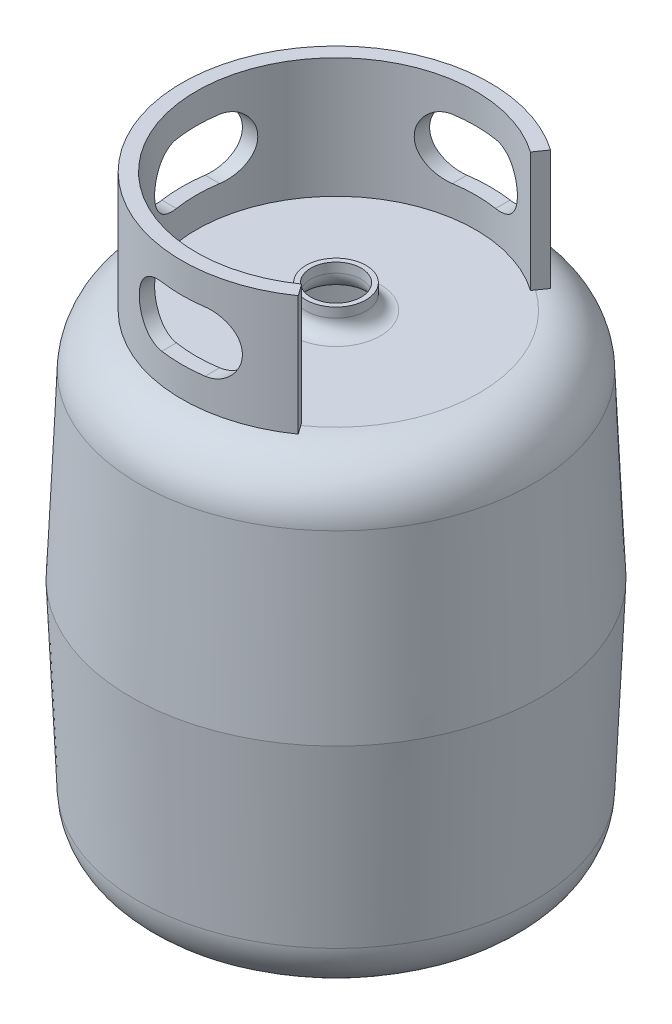
SolidWorks part; units mm, degrees
material "1060 Alloy"
ref_plane "Front Plane" through (0, 0, 0) normal (0, 0, 1) x (1, 0, 0)
ref_plane "Top Plane" through (0, 0, 0) normal (0, 1, 0) x (1, 0, 0)
ref_plane "Right Plane" through (0, 0, 0) normal (1, 0, 0) x (0, 0, -1)
sketch "Sketch6" plane through (0, 0, 0) normal (0, 0, 1) x (1, 0, 0)
  line L0 (0, -456.4408) -> (0, 456.4408) construction
  line L1 (-558.8873, 0) -> (558.8873, 0) construction
  line L2 (0, 213.75) -> (-25, 213.75)
  line L3 (-25, 213.75) -> (-25, 205.75)
  line L4 (-37, 193.75) -> (-119.4219, 193.75)
  line L5 (-164.379, 150.7129) -> (-170.9593, 0)
  line L6 (-170.9593, 0) -> (-164.379, -150.7129)
  line L7 (-119.4219, -193.75) -> (0, -193.75)
  line L8 (0, 213.75) -> (0, -193.75)
  arc A0 (-37, 193.75) -> (-25, 205.75) centre (-37, 205.75) ccw
  arc A1 (-164.379, -150.7129) -> (-119.4219, -193.75) centre (-119.4219, -148.75) ccw
  arc A2 (-119.4219, 193.75) -> (-164.379, 150.7129) centre (-119.4219, 148.75) ccw
  point P4 (0, 0)
  point P8 (0, 0)
  point P10 (-310.657, 0)
  point P18 (-25, 193.75)
  point P21 (-162.5, -193.75)
  point P24 (-162.5, 193.75)
  dimension "D9" = 12
  dimension "D10" = 45
  dimension "D1" = 387.5
  dimension "D2" = 25
  dimension "D3" = 20
  dimension "D4" = 162.5
  dimension "D5" = 162.5
  dimension "D6" = 193.75
  dimension "D7" = 193.75
  dimension "D8" = 92.5
revolve "Revolve2" add sketch "Sketch6" angle 360 about L8
shell "Shell8" thickness 4 removed face at (-25, 213.75, 0)
sketch "Sketch7" plane through (0, 193.75, 0) normal (0, 1, 0) x (1, 0, 0)
  line L0 (0, -178.349) -> (0, 178.349) construction
  line L1 (-198.7754, 0) -> (198.7754, 0) construction
  line L2 (0, 0) -> (73.6598, 105.197)
  line L3 (0, 0) -> (73.6598, -105.197)
  arc A0 (73.6598, 105.197) -> (73.6598, -105.197) centre (0, 0) ccw
  arc A1 (66.7768, 95.3672) -> (66.7768, -95.3672) centre (0, 0) ccw
  circle A2 centre (0, 0) radius 119.4219 construction
  point P9 (0, 0)
  point P12 (0, 0)
  circle M7 centre (0, 0) radius 119.4219
  dimension "D1" = 3
  dimension "D2" = 12
  dimension "D3" = 55
extrude "Boss-Extrude2" add sketch "Sketch7" along normal blind 100 contours L2 A0 L3 M7 | A1 L2 L3 M7 region at (-116.7258, 193.75, 0) region at (-122.69, 193.75, 0)
sketch "Sketch8" plane through (0, 0, 0) normal (0, 0, 1) x (1, 0, 0)
  line L0 (0, -377.172) -> (0, 377.172) construction
  line L1 (18, 243.75) -> (-18, 243.75) construction
  line L2 (18, 218.75) -> (-18, 218.75)
  line L3 (18, 268.75) -> (-18, 268.75)
  line L4 (66.7768, 293.75) -> (-116.4219, 293.75) construction
  arc A0 (18, 218.75) -> (18, 268.75) centre (18, 243.75) ccw
  arc A1 (-18, 268.75) -> (-18, 218.75) centre (-18, 243.75) ccw
  point P3 (43, 243.75)
  point P4 (0, 0)
  point P7 (0, 243.75)
  point P12 (-43, 243.75)
  dimension "D1" = 18
  dimension "D2" = 50
  dimension "D3" = 86
  dimension "D4" = 50
extrude "Cut-Extrude1" cut sketch "Sketch8" against normal blind 322 and the other way blind 417 contours L3 A1 L2 A0
sketch "Sketch9" plane through (0, 0, 0) normal (1, 0, 0) x (0, 0, -1)
  line L0 (0, 0) -> (0, 293.75) construction
  line L1 (116.4219, 293.75) -> (-116.4219, 293.75) construction
  line L2 (-18, 243.75) -> (18, 243.75) construction
  line L3 (-18, 268.75) -> (18, 268.75)
  line L4 (-18, 218.75) -> (18, 218.75)
  arc A0 (-18, 268.75) -> (-18, 218.75) centre (-18, 243.75) ccw
  arc A1 (18, 218.75) -> (18, 268.75) centre (18, 243.75) ccw
  point P7 (0, 243.75)
  point P12 (0, 0)
  point P13 (0, 0)
  point P14 (43, 243.75)
  point P15 (-43, 243.75)
  dimension "D1" = 50
  dimension "D2" = 86
  dimension "D3" = 50
extrude "Cut-Extrude2" cut sketch "Sketch9" against normal blind 322 contours L4 A1 L3 A0
